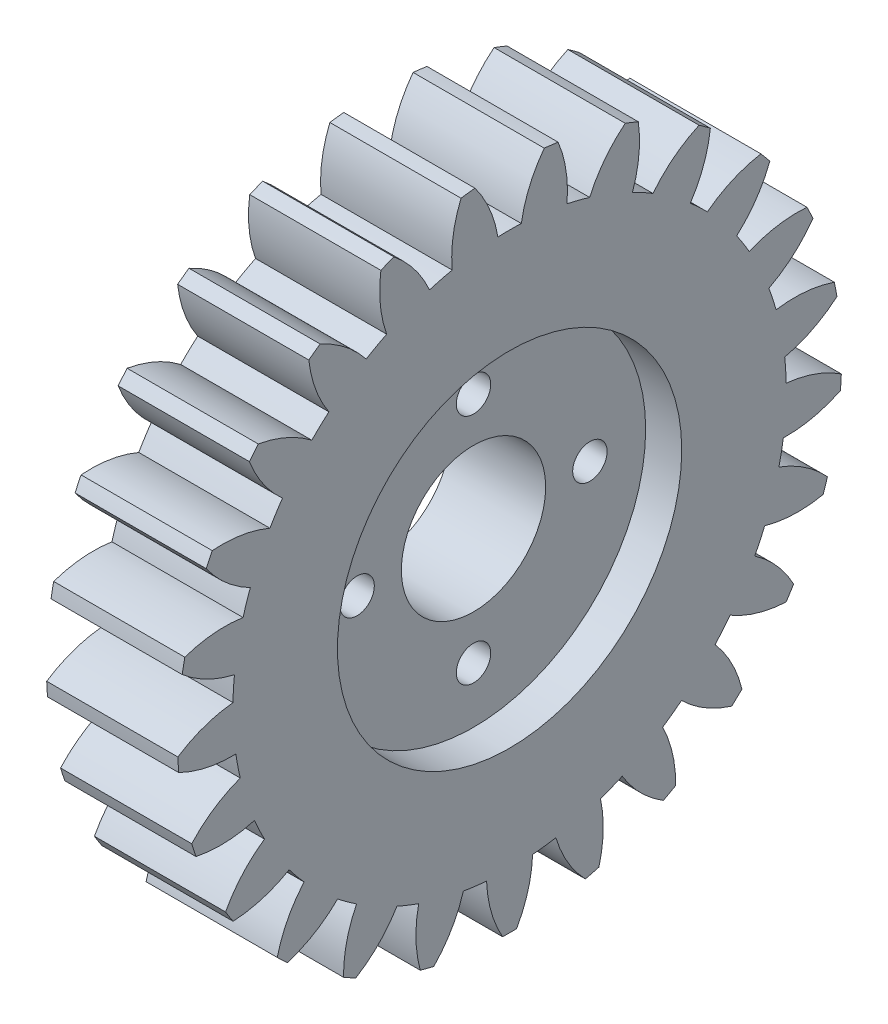
SolidWorks part; units mm, degrees
ref_plane "Plane1" through (0, 0, 0) normal (0, 0, 1) x (1, 0, 0)
ref_plane "Plane2" through (0, 0, 0) normal (0, 1, 0) x (1, 0, 0)
ref_plane "Plane3" through (0, 0, 0) normal (1, 0, 0) x (0, 0, -1)
other "Configuration Table"
sketch "HoldingSke" plane through (0, 0, 0) normal (0, 1, 0) x (1, 0, 0)
  line L0 (0, 0) -> (0.6042, -0.2817)
  line L1 (-15, 0) -> (100, 0) construction
  line L2 (0, 0) -> (-2.1039, 2.3779)
  line L3 (0, 0) -> (-11.863, 4.5341)
  line L4 (0, 0) -> (7.8269, 3.6497)
  line L5 (0, 0) -> (-46.8476, -17.4728)
  line L6 (0, 0) -> (-6.6317, -4.4744)
  line L7 (-2.1039, 2.3779) -> (8.6586, 51.2059)
  line L8 (-76.2, 54.61) -> (-76.1, 54.61)
  line L9 (-71.009, 38.7566) -> (-53.1078, 45.2721)
  line L10 (-76.2, 71.12) -> (104.1128, 71.12)
  line L11 (0, 0) -> (-8, 0)
  line L12 (-76.2, 101.6) -> (-76.147, 101.6)
  line L13 (24.9733, 27.94) -> (52.9518, 28.4284)
  line L14 (24.9733, 27.94) -> (24.9743, 27.94)
  line L15 (24.9733, 27.94) -> (100.4006, 29.5858)
  line L16 (-63.627, -1.5) -> (-12.827, -1.5)
  circle A0 centre (0, 0) radius 0.5
  circle A1 centre (0, 0) radius 16.874
  circle A2 centre (0, 0) radius 37.5
  circle A3 centre (0, 0) radius 0.5
  dimension "MHD" = 33.748
  dimension "Hub_dia" = 75
  dimension "Bore" = 1
  dimension "MBD" = 1
  dimension "Num_teeth" = 25
  dimension "Pitch" = 0.6667
  dimension "Overall_len" = 50
  dimension "Show_teeth" = 25
  dimension "Thickness" = 8
  dimension "OAL" = 50.0001
  dimension "T_dim" = 0.1
  dimension "Ap" = 20
  dimension "H" = 19.05
  dimension "Pitch_radius" = 180.3128
  dimension "Width" = 8
  dimension "Backlash" = 0.053
  dimension "Addendum_fac" = 1
  dimension "Dedendum_fac" = 1.25
  dimension "Clearance_fac" = 0.25
  dimension "Dedendum_add" = 0.001
  dimension "Module" = 1.5
sketch "BasProSke" plane through (0, 0, 0) normal (0, 1, 0) x (1, 0, 0)
  line L0 (-10, 0) -> (60, 0) construction
  line L1 (0, 0) -> (0, 20.25)
  line L2 (0, 0) -> (8, 0)
  line L3 (8, 0) -> (8, 20.25)
  line L4 (8, 20.25) -> (0, 20.25)
  dimension "Thickness" = 8
  dimension "Diameter" = 40.5
revolve "Base-Revolve" add sketch "BasProSke" angle 360 about L0
sketch "TooCutSke" plane through (0, 0, 0) normal (1, 0, 0) x (0, 0, -1)
  line L1 (0, 0) -> (0, 107) construction
  line L2 (0, 0) -> (-1.27, 18.7069) construction
  line L3 (0, 0) -> (-4.6921, 37.142) construction
  line L4 (-1.27, 18.7069) -> (-2.3461, 18.571) construction
  arc A0 (0.7139, 16.8589) -> (-0.7139, 16.8589) centre (0, 0) ccw
  arc A1 (2.1318, 20.163) -> (-2.1318, 20.163) centre (0, 0) ccw
  circle A2 centre (0, 0) radius 18.75 construction
  circle A3 centre (0, 0) radius 17.6192 construction
  arc A4 (-0.7139, 16.8589) -> (-2.1318, 20.163) centre (-8.1141, 15.6396) ccw
  arc A5 (2.1318, 20.163) -> (0.7139, 16.8589) centre (8.1141, 15.6396) ccw
  dimension "Root_dia" = 33.748
  dimension "Overcut_dia" = 40.5508
  dimension "Pitch_dia" = 37.5
  dimension "Base_dia" = 35.2385
  dimension "Flank_rad" = 7.5
  dimension "Half_ang" = 7.2
  dimension "Half_CT" = 1.0846
extrude "ToothCut" cut sketch "TooCutSke" along normal through all
fillet "Breaks" [suppressed] radius 0.03 tangent propagation no
fillet "RootFillets" [suppressed] radius 0.376
pattern_circular "TeethCuts" count 25 every 14.4 about axis through (-10, 0, 0) along (1, 0, 0) of "ToothCut", "RootFillets", "Breaks"
sketch "HubNeaOneSke" plane through (0, 0, 0) normal (-1, 0, 0) x (0, 0, 1)
  circle A0 centre (0, 0) radius 16.874
  dimension "Diameter" = 33.748
extrude "HubNearOne" [suppressed] add sketch "HubNeaOneSke" along normal blind 42.0001
sketch "HubNeaBotSke" plane through (0, 0, 0) normal (-1, 0, 0) x (0, 0, 1)
  circle A0 centre (0, 0) radius 16.874
  dimension "Diameter" = 33.748
extrude "HubNearBoth" [suppressed] add sketch "HubNeaBotSke" along normal blind 21
ref_plane "FarPln" through (8, 0, 0) normal (1, 0, 0) x (0, 0, -1)
sketch "HubFarSke" plane through (8, 0, 0) normal (1, 0, 0) x (0, 0, -1)
  circle A0 centre (0, 0) radius 16.874
  dimension "Diameter" = 33.748
extrude "HubFar" [suppressed] add sketch "HubFarSke" along normal blind 21
sketch "BorSke" plane through (0, 0, 0) normal (1, 0, 0) x (0, 0, -1)
  circle A0 centre (0, 0) radius 0.5
  dimension "Diameter" = 1
extrude "Bore" cut sketch "BorSke" along normal mid plane 100.0001
sketch "KeySke" plane through (0, 0, 0) normal (1, 0, 0) x (0, 0, -1)
  line L0 (-0.05, 0) -> (-0.05, 0.6)
  line L1 (-0.05, 0.6) -> (0.05, 0.6)
  line L2 (0.05, 0.6) -> (0.05, 0)
  line L3 (0, 0) -> (0, 34) construction
  line L4 (-0.05, 0) -> (0.05, 0)
  dimension "Offset" = 0.6
  dimension "Width" = 0.1
extrude "Keyway" [suppressed] cut sketch "KeySke" along normal mid plane 100.0001
pattern_circular "Keyway2" [suppressed] count 2 every 90 about axis through (-10, 0, 0) along (1, 0, 0) reverse direction yes
sketch "草图1" plane through (8, 0, 0) normal (1, 0, 0) x (0, 0, -1)
  circle A0 centre (0, 0) radius 10.5
  dimension "D1" = 21
extrude "切除-拉伸1" cut sketch "草图1" against normal blind 2.2
sketch "草图2" plane through (5.8, 0, 0) normal (1, 0, 0) x (0, 0, -1)
  line L0 (0, 0) -> (0, 5.0579) construction
  circle A0 centre (0, 0) radius 4.4
  circle A1 centre (0, 7.1) radius 1.05
  circle A2 centre (7.1, 0) radius 1.05
  circle A3 centre (0, -7.1) radius 1.05
  circle A4 centre (-7.1, 0) radius 1.05
  point P15 (0, 0)
  dimension "D1" = 8.8
  dimension "D2" = 2.1
  dimension "D3" = 7.1
  dimension "D4" = 4
extrude "切除-拉伸2" cut sketch "草图2" against normal through all
ref_axis "基准轴1" through (-4.4231, 0, 0) along (1, 0, 0)
equation "' \"Module@HoldingSke\" = 6.35"
equation "' \"Num_teeth@HoldingSke\" = 12"
equation "' \"Ap@HoldingSke\" =  20"
equation "' \"Ap@HoldingSke\" = 20"
equation "' \"Width@HoldingSke\" = 0.5 * 25.4"
equation "' \"Hub_dia@HoldingSke\"= 1 * 25.4"
equation "' \"Hub_dia@HoldingSke\" = 1 * 25.4"
equation "' \"Overall_len@HoldingSke\" = 1.0 * 25.4"
equation "' \"Bore@HoldingSke\" = 0.75 * 25.4"
equation "' \"T_dim@HoldingSke\" = 0.1 * 25.4"
equation "' \"Width@KeySke\" = 0.25 * 25.4"
equation "' \"Show_teeth@HoldingSke\" = 13"
equation "' \"Backlash@HoldingSke\" = 0.009 * 25.4"
equation "' \"Addendum_fac@HoldingSke\" = 1.0"
equation "' \"Dedendum_fac@HoldingSke\" = 1.25"
equation "' \"Dedendum_add@HoldingSke\" = 0.00005 * 25.4"
equation "' \"Clearance_fac@HoldingSke\" = 0.25"
equation "\"Pitch@HoldingSke\" = 1 / \"Module@HoldingSke\""
equation "\"Overcut_dia@TooCutSke\" = (\"Num_teeth@HoldingSke\" + 2 * \"Addendum_fac@HoldingSke\") / \"Pitch@HoldingSke\" + 0.002 * 25.4"
equation "\"Pitch_dia@TooCutSke\" = \"Num_teeth@HoldingSke\" / \"Pitch@HoldingSke\""
equation "\"Base_dia@TooCutSke\" = \"Num_teeth@HoldingSke\" / \"Pitch@HoldingSke\" * cos((\"Ap@HoldingSke\"  * 3.14159265 / 180))"
equation "\"Root_dia@TooCutSke\" = (\"Num_teeth@HoldingSke\" + 2) / \"Pitch@HoldingSke\" - 2 * (\"Addendum_fac@HoldingSke\" + \"Dedendum_fac@HoldingSke\") / \"Pitch@HoldingSke\" - \"Dedendum_add@HoldingSke\" * 2"
equation "\"Half_ang@TooCutSke\" = 180 / \"Num_teeth@HoldingSke\""
equation "\"Half_CT@TooCutSke\" = \"Num_teeth@HoldingSke\" / \"Pitch@HoldingSke\" * sin((3.14159265 / 2 / \"Num_teeth@HoldingSke\")) / 2 - 7 * \"Backlash@HoldingSke\" / 4"
equation "\"Flank_rad@TooCutSke\" = \"Num_teeth@HoldingSke\" / \"Pitch@HoldingSke\" / 5"
equation "\"Radius@RootFillets\" = \"Clearance_fac@HoldingSke\" / \"Pitch@HoldingSke\" + \"Dedendum_add@HoldingSke\""
equation "\"Break_rad@Breaks\" = 0.02 / \"Pitch@HoldingSke\""
equation "\"Thickness@HoldingSke\" = \"Width@HoldingSke\""
equation "\"OAL@HoldingSke\" = \"Thickness@HoldingSke\""
equation "\"MHD@HoldingSke\" = (\"Num_teeth@HoldingSke\" + 2) / \"Pitch@HoldingSke\" - 2 * (\"Addendum_fac@HoldingSke\" + \"Dedendum_fac@HoldingSke\")  / \"Pitch@HoldingSke\" - \"Dedendum_add@HoldingSke\" * 2"
equation "\"MBD@HoldingSke\" = (\"Num_teeth@HoldingSke\" + 2) / \"Pitch@HoldingSke\" - 2 * (\"Addendum_fac@HoldingSke\" + \"Dedendum_fac@HoldingSke\")  / \"Pitch@HoldingSke\" - \"Dedendum_add@HoldingSke\" * 2 - 0.002 * 25.4"
equation "\"MHD@HoldingSke\" = ((sgn( \"MHD@HoldingSke\" - \"Hub_dia@HoldingSke\" )-1)*( \"MHD@HoldingSke\" - \"Hub_dia@HoldingSke\" ))/-2+ \"Hub_dia@HoldingSke\""
equation "\"MBD@HoldingSke\" = ((sgn( \"MBD@HoldingSke\" - \"Bore@HoldingSke\" )-1)*( \"MBD@HoldingSke\" - \"Bore@HoldingSke\" ))/-2+ \"Bore@HoldingSke\""
equation "\"OAL@HoldingSke\" = ((sgn( \"OAL@HoldingSke\" - \"Overall_len@HoldingSke\" )+1)*( \"OAL@HoldingSke\" - \"Overall_len@HoldingSke\" ))/2 + \"Overall_len@HoldingSke\" + 0.000002 * 25.4"
equation "\"Num_teeth@TeethCuts\" = int( \"Show_teeth@HoldingSke\" ) + 1"
equation "\"Num_teeth@TeethCuts\" = ((sgn( \"Num_teeth@TeethCuts\" - \"Num_teeth@HoldingSke\" )-1)*( \"Num_teeth@TeethCuts\" - \"Num_teeth@HoldingSke\" ))/-2+ \"Num_teeth@HoldingSke\""
equation "\"Num_teeth@TeethCuts\" = ((sgn( \"Num_teeth@TeethCuts\" - 2.0)+1)*( \"Num_teeth@TeethCuts\" - 2.0))/2 +2.0"
equation "\"Angle@TeethCuts\" = 360.0 / \"Num_teeth@HoldingSke\""
equation "\"Diameter@BasProSke\" = (\"Num_teeth@HoldingSke\" + 2 * \"Addendum_fac@HoldingSke\") / \"Pitch@HoldingSke\""
equation "\"Thickness@BasProSke\"  = \"Thickness@HoldingSke\""
equation "' \"Fillet_rad@BasProSke\" =  \"Thickness@HoldingSke\" * 0.05"
equation "' \"Fillet_rad@BasProSke\" = \"Thickness@HoldingSke\" * 0.05"
equation "\"MHD@HoldingSke\" = ((sgn( \"MHD@HoldingSke\" - \"Root_dia@TooCutSke\" )-1)*( \"MHD@HoldingSke\" - \"Root_dia@TooCutSke\" ))/-2+ \"Root_dia@TooCutSke\""
equation "\"Diameter@HubNeaOneSke\" = \"MHD@HoldingSke\""
equation "\"Length@HubNearOne\" = \"OAL@HoldingSke\" - \"Thickness@BasProSke\""
equation "\"Diameter@HubNeaBotSke\" = \"MHD@HoldingSke\""
equation "\"Length@HubNearBoth\" = ( \"OAL@HoldingSke\" - \"Thickness@BasProSke\" ) / 2.0"
equation "\"Thickness@FarPln\" = \"Thickness@BasProSke\""
equation "\"Diameter@HubFarSke\" = \"MHD@HoldingSke\""
equation "\"Length@HubFar\" = ( \"OAL@HoldingSke\" - \"Thickness@BasProSke\" ) / 2.0"
equation "\"Diameter@BorSke\" = \"MBD@HoldingSke\""
equation "\"D1@Bore\" = \"OAL@HoldingSke\" * 2.0"
equation "\"D1@Keyway\" = \"OAL@HoldingSke\" * 2.0"
equation "\"Offset@KeySke\" = \"T_dim@HoldingSke\" + \"MBD@HoldingSke\" / 2.0"
